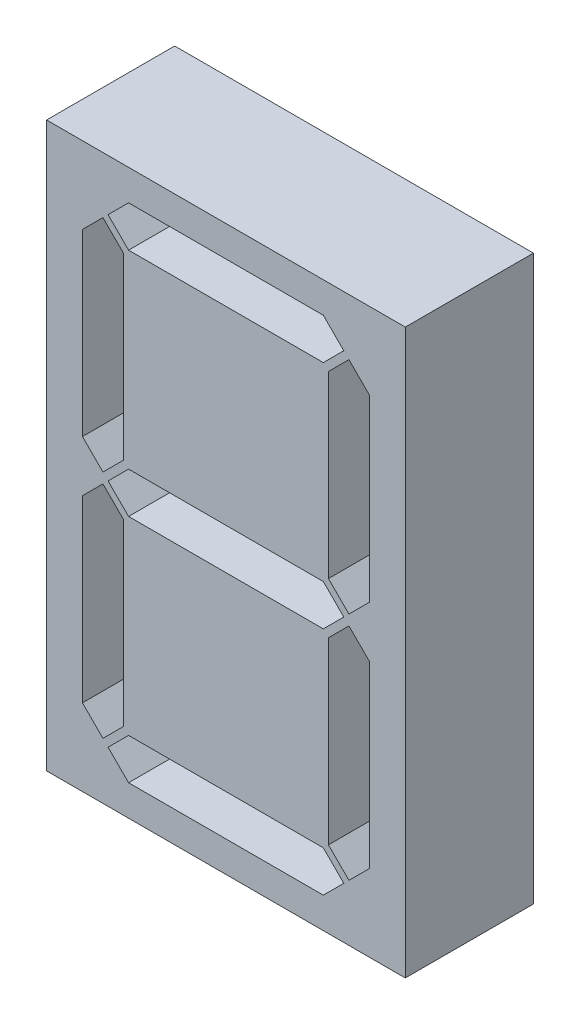
SolidWorks part; units mm, degrees
ref_plane "Front Plane" through (0, 0, 0) normal (0, 0, 1) x (1, 0, 0)
ref_plane "Top Plane" through (0, 0, 0) normal (0, 1, 0) x (1, 0, 0)
ref_plane "Right Plane" through (0, 0, 0) normal (1, 0, 0) x (0, 0, -1)
sketch "Sketch1" plane through (0, 0, 0) normal (0, 0, 1) x (1, 0, 0)
  line L1 (0, 0) -> (70, 0)
  line L2 (0, 0) -> (0, 110)
  line L3 (0, 110) -> (70, 110)
  line L4 (70, 0) -> (70, 110)
  dimension "D1" = 110
  dimension "D2" = 70
extrude "Boss-Extrude1" add sketch "Sketch1" along normal blind 25
sketch "Sketch2" plane through (0, 0, 0) normal (0, 0, -1) x (-1, 0, 0)
  line L0 (-70, 0) -> (-70, 110) construction
  line L1 (-65.2, 4.8) -> (-4.8, 4.8)
  line L2 (-65.2, 4.8) -> (-65.2, 105.2)
  line L3 (-65.2, 105.2) -> (-4.8, 105.2)
  line L4 (-4.8, 4.8) -> (-4.8, 105.2)
  line L5 (-70, 110) -> (0, 110) construction
  line L6 (0, 0) -> (-70, 0) construction
  line L7 (0, 110) -> (0, 0) construction
  dimension "D1" = 4.8
  dimension "D2" = 4.8
  dimension "D3" = 4.8
  dimension "D4" = 4.8
extrude "Cut-Extrude1" cut sketch "Sketch2" against normal blind 1.6
fillet "Fillet1" radius 3 4 edges at (4.8, 105.2, 0.8) (4.8, 4.8, 0.8) (65.2, 4.8, 0.8) (65.2, 105.2, 0.8)
sketch "Sketch3" plane through (0, 0, 1.6) normal (0, 0, -1) x (-1, 0, 0)
  line L6 (-70, 110) -> (0, 110) construction
  line L7 (-70, 0) -> (-70, 110) construction
  line L8 (13.75, 0) -> (-13.75, 0) construction
  circle A0 centre (-61.5, 101.5) radius 2
  circle A1 centre (-61.5, 8.5) radius 2
  circle A2 centre (-8.5, 8.5) radius 2
  circle A5 centre (-8.5, 101.5) radius 2
  point P10 (0, 0)
  dimension "D3" = 53
  dimension "D17" = 4
  dimension "D18" = 4
  dimension "D19" = 4
  dimension "D20" = 4
  dimension "D4" = 8.5
  dimension "D5" = 8.5
  dimension "D6" = 8.5
  dimension "D7" = 8.5
  dimension "D8" = 8.5
  dimension "D9" = 93
  dimension "D11" = 53
sketch "Sketch5" plane through (0, 0, 1.6) normal (0, 0, -1) x (-1, 0, 0)
  line L1 (-54, 14) -> (-16, 14)
  line L2 (-54, 14) -> (-54, 6)
  line L3 (-54, 6) -> (-16, 6)
  line L4 (-16, 14) -> (-16, 6)
  line L5 (-54, 6) -> (-58, 10)
  line L6 (-58, 10) -> (-54, 14)
  line L7 (-16, 14) -> (-12, 10)
  line L8 (-12, 10) -> (-16, 6)
  line L10 (-16, 59) -> (-16, 51)
  line L11 (-58, 55) -> (-54, 59)
  line L12 (-12, 55) -> (-16, 51)
  line L13 (-54, 59) -> (-16, 59)
  line L14 (-16, 59) -> (-12, 55)
  line L15 (-54, 59) -> (-54, 51)
  line L16 (-54, 51) -> (-16, 51)
  line L17 (-54, 51) -> (-58, 55)
  line L18 (-16, 104) -> (-16, 96)
  line L19 (-58, 100) -> (-54, 104)
  line L20 (-12, 100) -> (-16, 96)
  line L21 (-54, 104) -> (-16, 104)
  line L22 (-16, 104) -> (-12, 100)
  line L23 (-54, 104) -> (-54, 96)
  line L24 (-54, 96) -> (-16, 96)
  line L25 (-54, 96) -> (-58, 100)
  line L26 (-70, 0) -> (-70, 110) construction
  line L28 (13.75, 0) -> (-13.75, 0) construction
  dimension "D1" = 38
  dimension "D2" = 8
  dimension "D4" = 4
  dimension "D5" = 4
  dimension "D6" = 46
  dimension "D7" = 4
  dimension "D8" = 12
  dimension "D9" = 38
  dimension "D10" = 8
  dimension "D11" = 4
  dimension "D12" = 4
  dimension "D13" = 46
  dimension "D14" = 4
  dimension "D15" = 38
  dimension "D16" = 8
  dimension "D17" = 4
  dimension "D18" = 4
  dimension "D19" = 46
  dimension "D20" = 4
  dimension "D21" = 12
  dimension "D22" = 12
  dimension "D23" = 6
  dimension "D39" = 37
  dimension "D41" = 37
extrude "Cut-Extrude4" cut sketch "Sketch5" against normal through all contours L23 L24 L18 L21 | L25 L23 L19 | L22 L18 L20 | L15 L16 L10 L13 | L17 L15 L11 | L14 L10 L12 | L4 L1 L2 L3 | L6 L5 L2 | L8 L7 L4 region at (35, 10, 1.6) region at (55.3333, 10, 1.6) region at (14.6667, 10, 1.6) region at (14.6667, 55, 1.6) region at (35, 55, 1.6) region at (55.3333, 55, 1.6) region at (14.6667, 100, 1.6) region at (35, 100, 1.6) region at (55.3333, 100, 1.6)
sketch "Sketch6" plane through (0, 0, 1.6) normal (0, 0, -1) x (-1, 0, 0)
  line L1 (-55, 15) -> (-63, 15)
  line L2 (-55, 15) -> (-55, 50)
  line L3 (-55, 50) -> (-63, 50)
  line L4 (-63, 15) -> (-63, 50)
  line L5 (-63, 15) -> (-59, 11)
  line L6 (-59, 11) -> (-55, 15)
  line L7 (-63, 50) -> (-59, 54)
  line L8 (-59, 54) -> (-55, 50)
  line L9 (-15, 50) -> (-11, 54)
  line L10 (-7, 15) -> (-15, 15)
  line L11 (-7, 50) -> (-15, 50)
  line L12 (-4.8, 7.8) -> (-4.8, 102.2) construction
  line L13 (-62.2, 4.8) -> (-7.8, 4.8) construction
  line L14 (-15, 15) -> (-11, 11)
  line L15 (-15, 15) -> (-15, 50)
  line L16 (-11, 11) -> (-7, 15)
  line L17 (-11, 54) -> (-7, 50)
  line L18 (-7, 15) -> (-7, 50)
  line L19 (-70, 110) -> (0, 110) construction
  line L22 (-70, 0) -> (-70, 110) construction
  line L24 (0, 0) -> (-70, 0) construction
  line L25 (13.75, 0) -> (-13.75, 0) construction
  line L35 (-63, 95) -> (-59, 99)
  line L36 (-55, 60) -> (-63, 60)
  line L37 (-55, 95) -> (-63, 95)
  line L38 (-63, 60) -> (-59, 56)
  line L39 (-63, 60) -> (-63, 95)
  line L40 (-59, 56) -> (-55, 60)
  line L41 (-59, 99) -> (-55, 95)
  line L42 (-55, 60) -> (-55, 95)
  line L43 (-15, 95) -> (-11, 99)
  line L44 (-7, 60) -> (-15, 60)
  line L45 (-7, 95) -> (-15, 95)
  line L46 (-15, 60) -> (-11, 56)
  line L47 (-15, 60) -> (-15, 95)
  line L48 (-11, 56) -> (-7, 60)
  line L49 (-11, 99) -> (-7, 95)
  line L50 (-7, 60) -> (-7, 95)
  dimension "D1" = 35
  dimension "D3" = 8
  dimension "D4" = 11
  dimension "D5" = 4
  dimension "D6" = 4
  dimension "D7" = 4
  dimension "D8" = 4
  dimension "D9" = 11
  dimension "D10" = 8
  dimension "D11" = 11
  dimension "D12" = 4
  dimension "D13" = 4
  dimension "D14" = 4
  dimension "D15" = 4
  dimension "D16" = 4
  dimension "D17" = 7
  dimension "D18" = 7
  dimension "D19" = 11
  dimension "D20" = 4
  dimension "D21" = 35
  dimension "D22" = 35
  dimension "D27" = 35
  dimension "D28" = 8
  dimension "D29" = 4
  dimension "D30" = 4
  dimension "D31" = 4
  dimension "D32" = 4
  dimension "D34" = 8
  dimension "D36" = 4
  dimension "D37" = 4
  dimension "D51" = 40
  dimension "D58" = 40
extrude "Cut-Extrude5" cut sketch "Sketch6" against normal through all contours L36 L42 L37 L39 | L41 L35 L37 | L38 L40 L36 | L8 L7 L3 | L4 L1 L2 L3 | L5 L6 L1 | L10 L18 L11 L15 | L14 L16 L10 | L17 L9 L11 | L46 L48 L44 | L44 L50 L45 L47 | L49 L43 L45 region at (59, 13.6667, 1.6) region at (59, 32.5, 1.6) region at (59, 51.3333, 1.6) region at (11, 51.3333, 1.6) region at (11, 32.5, 1.6) region at (11, 13.6667, 1.6) region at (59, 96.3333, 1.6) region at (59, 77.5, 1.6) region at (59, 58.6667, 1.6) region at (11, 96.3333, 1.6) region at (11, 77.5, 1.6) region at (11, 58.6667, 1.6)
sketch "Sketch7" plane through (0, 0, 1.6) normal (0, 0, -1) x (-1, 0, 0)
  line L0 (-55, 95) -> (-54, 96)
  line L1 (-54, 96) -> (-16, 96)
  line L2 (-16, 96) -> (-15, 95)
  line L3 (-15, 95) -> (-15, 60)
  line L4 (-15, 60) -> (-16, 59)
  line L5 (-16, 59) -> (-12, 55) construction
  line L6 (-16, 59) -> (-54, 59)
  line L7 (-54, 59) -> (-55, 60)
  line L8 (-55, 60) -> (-55, 95)
  line L37 (-54, 14) -> (-55, 15)
  line L38 (-55, 15) -> (-55, 50)
  line L39 (-55, 50) -> (-54, 51)
  line L40 (-54, 51) -> (-16, 51)
  line L41 (-16, 51) -> (-15, 50)
  line L42 (-15, 50) -> (-15, 15)
  line L43 (-15, 15) -> (-16, 14)
  line L44 (-16, 14) -> (-54, 14)
extrude "Cut-Extrude6" cut sketch "Sketch7" against normal blind 1
extrude "Cut-Extrude7" cut sketch "Sketch3" against normal blind 3.5
sketch "Sketch8" plane through (0, 0, 2.6) normal (0, 0, -1) x (-1, 0, 0)
  line L0 (-55, 95) -> (-55, 60) construction
  line L1 (-52, 62) -> (-18, 62)
  line L2 (-52, 62) -> (-52, 93)
  line L3 (-52, 93) -> (-18, 93)
  line L4 (-18, 62) -> (-18, 93)
  line L5 (-16, 96) -> (-54, 96) construction
  line L6 (-15, 60) -> (-15, 95) construction
  line L7 (-54, 59) -> (-16, 59) construction
  line L8 (-55, 50) -> (-55, 15) construction
  line L9 (-52, 48) -> (-18, 48)
  line L10 (-52, 48) -> (-52, 17)
  line L11 (-52, 17) -> (-18, 17)
  line L12 (-18, 48) -> (-18, 17)
  line L13 (-16, 51) -> (-54, 51) construction
  line L14 (-15, 15) -> (-15, 50) construction
  line L15 (-54, 14) -> (-16, 14) construction
  dimension "D1" = 3
  dimension "D2" = 3
  dimension "D3" = 3
  dimension "D4" = 3
  dimension "D5" = 3
  dimension "D6" = 3
  dimension "D7" = 3
  dimension "D8" = 3
extrude "Boss-Extrude2" add sketch "Sketch8" along normal up to surface (1 mm away) up to face at (6.5, 101.5, 1.6)
